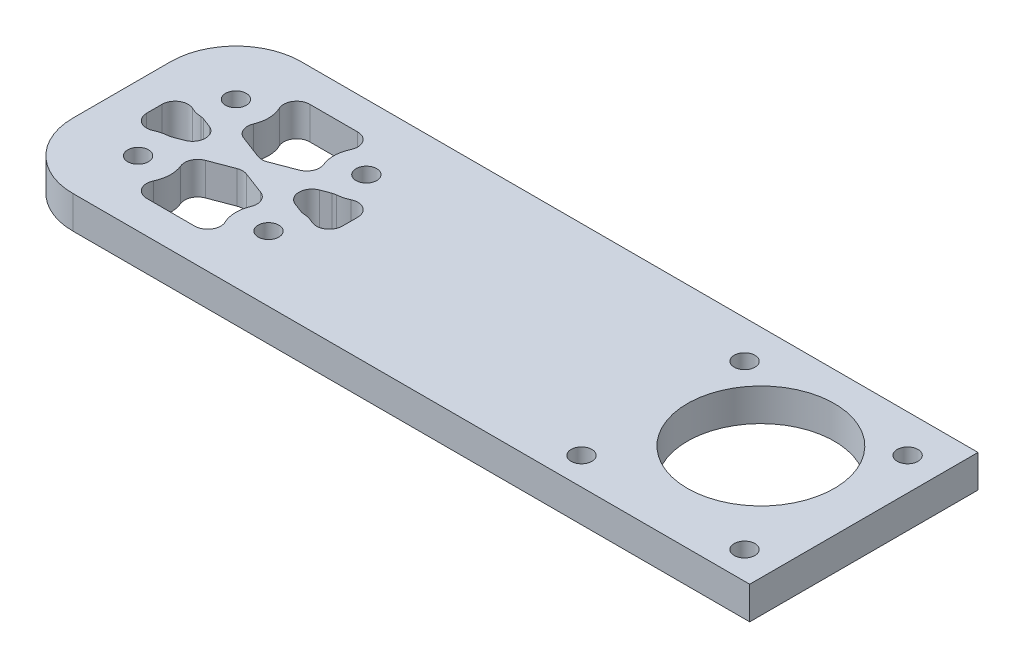
SolidWorks part; units mm, degrees
material "6061-T6 (SS)"
ref_plane "Front Plane" through (0, 0, 0) normal (0, 0, 1) x (1, 0, 0)
ref_plane "Top Plane" through (0, 0, 0) normal (0, 1, 0) x (1, 0, 0)
ref_plane "Right Plane" through (0, 0, 0) normal (1, 0, 0) x (0, 0, -1)
sketch "Sketch1" plane through (0, 0, 0) normal (0, 1, 0) x (1, 0, 0)
  line L0 (59.544, 22.225) -> (84.944, 22.225)
  line L1 (-59.5439, -22.225) -> (59.544, -22.225)
  line L2 (-59.5439, -22.225) -> (-59.5439, 22.225)
  line L3 (-59.5439, 22.225) -> (59.544, 22.225)
  line L5 (-59.5439, -22.225) -> (59.544, 22.225) construction
  line L6 (-59.5439, 22.225) -> (59.544, -22.225) construction
  line L7 (84.944, 22.225) -> (84.944, -22.225)
  line L8 (84.944, -22.225) -> (59.544, -22.225)
  point P0 (0, 0)
  dimension "D1" = 119.0879
  dimension "D2" = 44.45
  dimension "D3" = 25.4
extrude "Boss-Extrude1" add sketch "Sketch1" along normal blind 6.35
sketch "Sketch2" plane through (0, 6.35, 0) normal (0, 1, 0) x (1, 0, 0)
  line L4 (84.944, 22.225) -> (-59.5439, 22.225) construction
  line L5 (-59.5439, -22.225) -> (84.944, -22.225) construction
  line L7 (-8.7439, 22.225) -> (-8.7439, -22.225) construction
  line L8 (-59.5439, 22.225) -> (-59.5439, -22.225) construction
  dimension "D1" = 50.8
hole_wizard "#10-32 Tapped Hole2" positions "Sketch3" profile "Sketch4" tap size "#10-32" standard "ANSI Inch" end condition through all
sketch "Sketch3" plane through (0, 6.35, 0) normal (0, 1, 0) x (1, 0, 0)
  line L4 (-46.8439, 22.225) -> (-46.8439, -22.225) construction
  line L5 (84.944, 22.225) -> (-59.5439, 22.225) construction
  line L6 (-59.5439, -22.225) -> (84.944, -22.225) construction
  line L8 (-21.4439, 22.225) -> (-21.4439, -22.225) construction
  line L9 (-59.5439, 22.225) -> (-59.5439, -22.225) construction
  line L11 (-59.5439, 9.525) -> (-8.7439, 9.525) construction
  line L13 (-59.5439, -9.525) -> (-8.7439, -9.525) construction
  point P0 (-46.8439, 9.525)
  point P2 (-21.4439, 9.525)
  point P4 (-21.4439, -9.525)
  point P6 (-46.8439, -9.525)
  dimension "D1" = 12.7
  dimension "D2" = 38.1
  dimension "D3" = 12.7
  dimension "D4" = 12.7
  dimension "D5" = 50.8
  dimension "D6" = 50.8
sketch "Sketch4" plane through (-46.8439, 6.35, -9.525) normal (1, 0, 0) x (0, 0, 1)
  line L0 (0, 0) -> (0, 6.35)
  line L1 (0, 6.35) -> (2.0193, 6.35)
  line L2 (2.0193, 6.35) -> (2.0193, 0)
  line L5 (2.0193, 0) -> (0, 0)
  line L11 (0, -6.35) -> (0, 107.95) construction
  dimension "Thru Tap Drill Dia." = 4.0386
  dimension "Thru Tap Drill Depth" = 6.35
cosmetic thread "Hole Thread3" parameters "D2"=4.826
cosmetic thread "Hole Thread4" parameters "D2"=4.826
cosmetic thread "Hole Thread5" parameters "D2"=4.826
cosmetic thread "Hole Thread6" parameters "D2"=4.826
sketch "Sketch5" plane through (0, 6.35, 0) normal (0, 1, 0) x (1, 0, 0)
  line L1 (84.944, -22.225) -> (84.944, 22.225) construction
  line L2 (59.417, -12.7635) -> (84.944, -12.7635)
  line L4 (59.417, -12.7635) -> (59.417, 12.7635)
  line L5 (59.417, 12.7635) -> (84.944, 12.7635)
  line L6 (84.944, -12.7635) -> (84.944, 12.7635)
  line L7 (59.417, -12.7635) -> (84.944, 12.7635) construction
  line L8 (59.417, 12.7635) -> (84.944, -12.7635) construction
  line L13 (84.944, 12.7635) -> (84.944, 22.225) construction
  line L14 (84.944, -12.7635) -> (84.944, -22.225) construction
  dimension "D3" = 25.527
fillet "Fillet2" radius 12.7 2 edges at (-59.5439, 3.175, -22.225) (-59.5439, 3.175, 22.225)
sketch "Sketch11" plane through (0, 6.35, 0) normal (0, 1, 0) x (1, 0, 0)
  line L0 (-46.8439, 15.875) -> (-21.4439, 15.875)
  line L1 (-15.0939, -9.525) -> (-15.0939, 9.525)
  line L2 (-53.1939, 9.525) -> (-53.1939, -9.525)
  line L3 (-46.8439, -15.875) -> (-21.4439, -15.875)
  line L4 (-46.9965, -3.1768) -> (-38.6205, 0)
  line L5 (-21.2914, 3.1768) -> (-29.6674, 0)
  line L6 (-46.9965, 3.1768) -> (-38.6205, 0)
  line L7 (-21.2914, -3.1768) -> (-29.6674, 0)
  line L8 (-34.1439, 1.6978) -> (-25.768, 4.8747)
  line L9 (-34.1439, -1.6978) -> (-42.5199, -4.8747)
  line L10 (-34.1439, 1.6978) -> (-42.5199, 4.8747)
  line L11 (-34.1439, -1.6978) -> (-25.768, -4.8747)
  arc A0 (-42.5199, 4.8747) -> (-46.8439, 15.875) centre (-46.8439, 9.525) ccw
  arc A1 (-21.2914, 3.1768) -> (-15.0939, 9.525) centre (-21.4439, 9.525) ccw
  arc A2 (-25.768, -4.8747) -> (-21.4439, -15.875) centre (-21.4439, -9.525) ccw
  arc A3 (-46.9965, -3.1768) -> (-53.1939, -9.525) centre (-46.8439, -9.525) ccw
  arc A4 (-46.8439, -15.875) -> (-42.5199, -4.8747) centre (-46.8439, -9.525) ccw
  arc A5 (-53.1939, 9.525) -> (-46.9965, 3.1768) centre (-46.8439, 9.525) ccw
  arc A6 (-21.4439, 15.875) -> (-25.768, 4.8747) centre (-21.4439, 9.525) ccw
  arc A7 (-15.0939, -9.525) -> (-21.2914, -3.1768) centre (-21.4439, -9.525) ccw
  dimension "D1" = 12.7
  dimension "D2" = 3.175
  dimension "D3" = 3.175
extrude "Cut-Extrude3" cut sketch "Sketch11" against normal through all
fillet "Fillet3" radius 2.54 20 edges at (-15.0939, 3.175, -9.525) (-15.0939, 3.175, 9.525) (-21.2914, 3.175, 3.1768) (-29.6674, 3.175, 0) (-21.2914, 3.175, -3.1768) (-46.8439, 3.175, -15.875) (-21.4439, 3.175, -15.875) (-25.768, 3.175, -4.8747) (-34.1439, 3.175, -1.6978) (-38.6205, 3.175, 0) (-46.9965, 3.175, 3.1768) (-53.1939, 3.175, 9.525) (-53.1939, 3.175, -9.525) (-46.9965, 3.175, -3.1768) (-42.5199, 3.175, 4.8747) (-34.1439, 3.175, 1.6978) (-25.768, 3.175, 4.8747) (-21.4439, 3.175, 15.875) (-46.8439, 3.175, 15.875) (-42.5199, 3.175, -4.8747)
sketch "Sketch12" plane through (0, 6.35, 0) normal (0, 1, 0) x (1, 0, 0)
  line L0 (62.719, 2.175) -> (84.944, 2.175) construction
  line L2 (84.944, -22.225) -> (84.944, 22.225) construction
  line L4 (84.944, 22.225) -> (-46.8439, 22.225) construction
  circle A0 centre (62.719, 2.175) radius 14.3129
  dimension "D1" = 28.6258
  dimension "D2" = 22.225
  dimension "D3" = 20.05
extrude "Cut-Extrude4" cut sketch "Sketch12" against normal through all
sketch "Sketch13" plane through (0, 6.35, 0) normal (0, 1, 0) x (1, 0, 0)
  line L0 (62.719, 2.175) -> (62.719, -1) construction
  line L1 (84.944, -22.225) -> (84.944, 22.225) construction
  line L2 (46.844, -16.875) -> (78.594, -16.875) construction
  line L3 (46.844, -16.875) -> (46.844, 14.875) construction
  line L4 (46.844, 14.875) -> (78.594, 14.875) construction
  line L5 (78.594, -16.875) -> (78.594, 14.875) construction
  line L6 (46.844, -16.875) -> (78.594, 14.875) construction
  line L7 (46.844, 14.875) -> (78.594, -16.875) construction
  circle A0 centre (78.594, 14.875) radius 2.0193
  circle A1 centre (46.844, 14.875) radius 2.0193
  circle A2 centre (46.844, -16.875) radius 2.0193
  circle A3 centre (78.594, -16.875) radius 2.0193
  dimension "D3" = 4.0386
  dimension "D1" = 3.175
  dimension "D2" = 6.35
extrude "Cut-Extrude5" cut sketch "Sketch13" against normal through all
